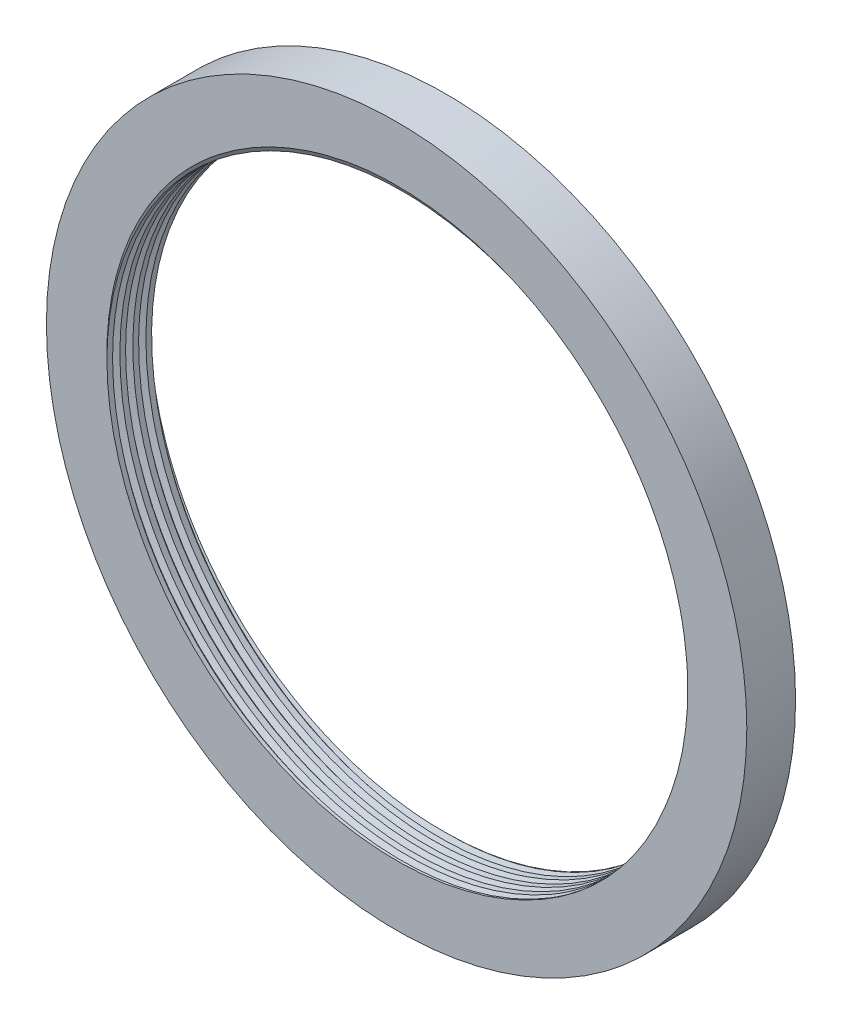
SolidWorks part; units mm, degrees
ref_plane "Front Plane" through (0, 0, 0) normal (0, 0, 1) x (1, 0, 0)
ref_plane "Top Plane" through (0, 0, 0) normal (0, 1, 0) x (1, 0, 0)
ref_plane "Right Plane" through (0, 0, 0) normal (1, 0, 0) x (0, 0, -1)
sketch "Sketch1" plane through (0, 0, 0) normal (0, 0, 1) x (1, 0, 0)
  circle A0 centre (0, 0) radius 53.85
  circle A1 centre (0, 0) radius 44.55
  dimension "D1" = 107.7
  dimension "D2" = 9.3
extrude "Boss-Extrude1" add sketch "Sketch1" along normal blind 7.5
thread "Thread1" pitch 1.5 start angle 0, offset 0, length 10, pitch 2, diameter 89.1
ref_plane "Plane1" through (-44.55, 0, 7.5) normal (0, 1, 0) x (-1, 0, 0)
sketch "Thread Profile1" plane through (-44.55, 0, 7.5) normal (0, 1, 0) x (-1, 0, 0)
  line L0 (0, 0) -> (0, 1.5) construction
  line L1 (0, 0) -> (0.8119, 0.4687)
  line L2 (0.8119, 0.4687) -> (0.8119, 0.6562)
  line L3 (0.8119, 0.6562) -> (0, 1.125)
  line L4 (0.8119, 0.5625) -> (0, 0.5625) construction
  line L11 (0, 0) -> (0, 1.125)
  point P2 (0, 0)
  dimension "Pitch" = 1.5
  dimension "Profile_Angle" = 60
  dimension "Profile_Land" = 0.1875
  dimension "Profile_Height" = 0.8119
